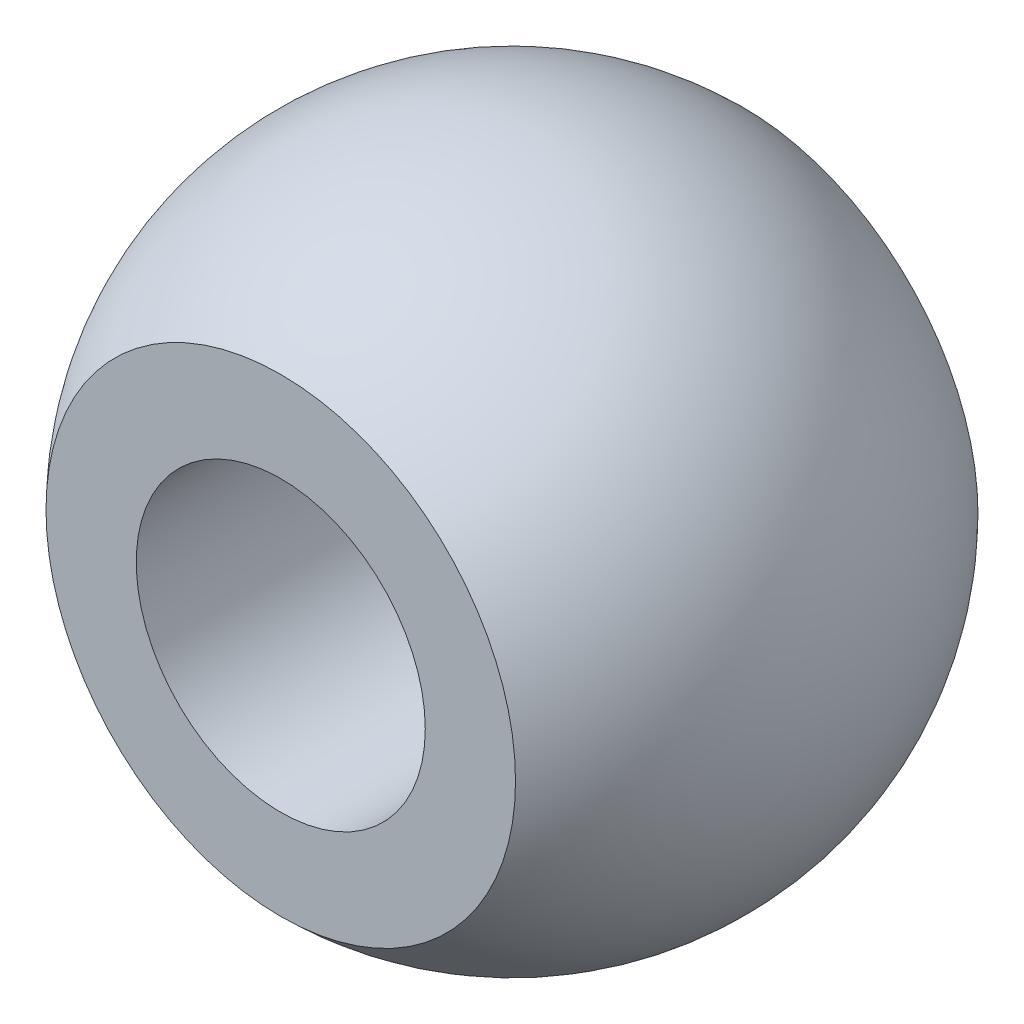
SolidWorks part; units mm, degrees
ref_plane "Front" through (0, 0, 0) normal (0, 0, 1) x (1, 0, 0)
ref_plane "Top" through (0, 0, 0) normal (0, 1, 0) x (1, 0, 0)
ref_plane "Right" through (0, 0, 0) normal (1, 0, 0) x (0, 0, -1)
sketch "Sketch1" plane through (0, 0, 0) normal (0, 0, 1) x (1, 0, 0)
  line L0 (0, 5.7) -> (0, -5.7) construction
  line L1 (0, 5.7) -> (0, -2.5)
  line L2 (0, -2.5) -> (0, -5.7)
  arc A0 (0, 5.7) -> (0, -5.7) centre (0, 0) ccw
ref_axis "Axis1" through (0, 50, 0) along (0, -1, 0)
revolve "Revolve3" add sketch "Sketch1" angle 360 about L0
sketch "Sketch2" plane through (0, 0, 0) normal (0, 1, 0) x (1, 0, 0)
  line L0 (0, 0) -> (0, 4) construction
  line L1 (-6.321, 4) -> (7.4056, 4)
  line L2 (7.4056, 4) -> (7.4056, 7.7682)
  line L3 (7.4056, 7.7682) -> (-6.321, 7.7682)
  line L4 (-6.321, 7.7682) -> (-6.321, 4)
  line L5 (-2.7955, 0) -> (4.0099, 0) construction
  line L6 (7.4056, -4) -> (7.4056, -7.7682)
  line L7 (-6.321, -4) -> (7.4056, -4)
  line L8 (-6.321, -7.7682) -> (-6.321, -4)
  line L9 (7.4056, -7.7682) -> (-6.321, -7.7682)
  dimension "D1" = 4
extrude "Cut-Extrude1" cut sketch "Sketch2" against normal through all both and the other way through all
sketch "Sketch3" plane through (0, 0, 4) normal (0, 0, 1) x (1, 0, 0)
  circle A0 centre (0, 0) radius 2.5
extrude "Cut-Extrude2" cut sketch "Sketch3" against normal blind 10
